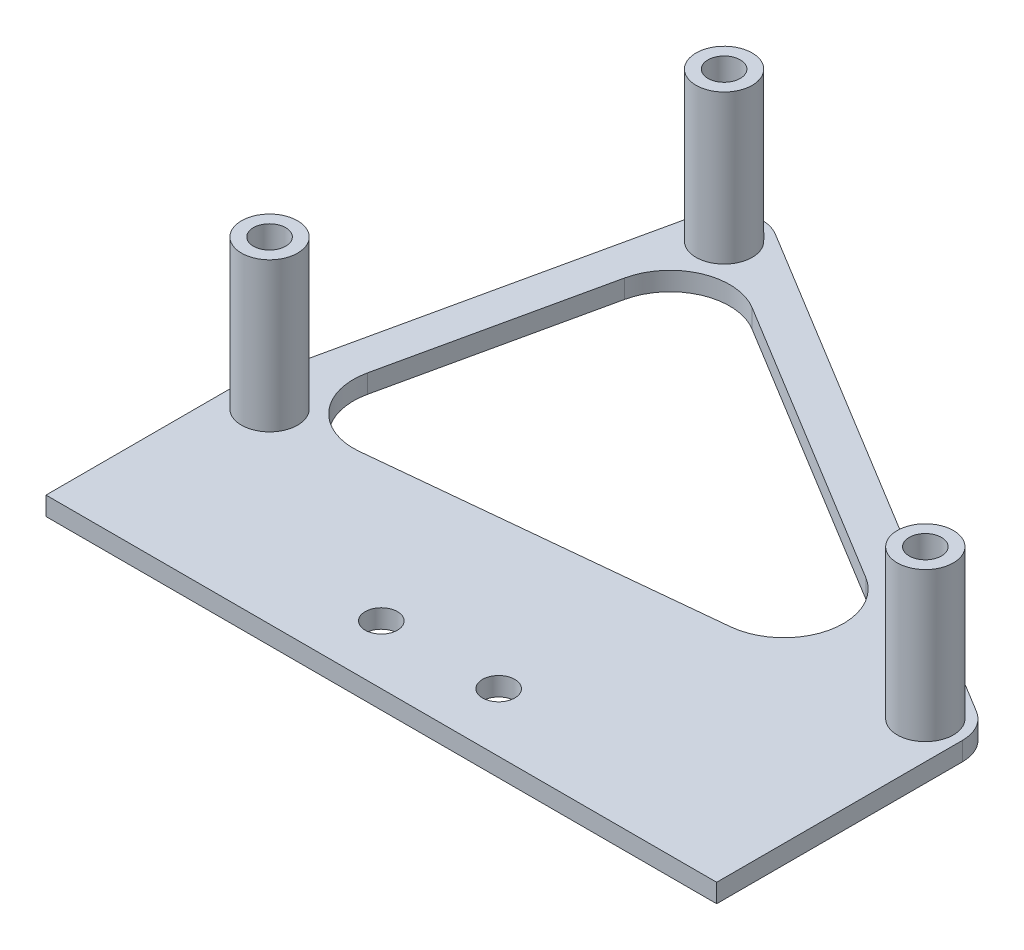
SolidWorks part; units mm, degrees
ref_plane "Front Plane" through (0, 0, 0) normal (0, 0, 1) x (1, 0, 0)
ref_plane "Top Plane" through (0, 0, 0) normal (0, 1, 0) x (1, 0, 0)
ref_plane "Right Plane" through (0, 0, 0) normal (1, 0, 0) x (0, 0, -1)
sketch "Sketch1" plane through (0, 0, 0) normal (0, 1, 0) x (1, 0, 0)
  line L0 (-54.2925, -20.955) -> (-40.3225, 42.545) construction
  line L5 (-40.3225, 42.545) -> (47.3075, -10.795) construction
  line L6 (47.3075, -10.795) -> (-54.2925, -20.955) construction
  line L7 (-47.3075, 10.795) -> (47.3075, -10.795) construction
  circle A0 centre (-40.3225, 42.545) radius 2.75
  circle A1 centre (-54.2925, -20.955) radius 2.75
  circle A2 centre (47.3075, -10.795) radius 2.75
  point P8 (0, 0)
  dimension "D5" = 5.5
  dimension "D1" = 10.16
  dimension "D2" = 101.6
  dimension "D3" = 13.97
  dimension "D4" = 63.5
sketch "Sketch2" plane through (0, 0, 0) normal (0, 1, 0) x (1, 0, 0)
  line L6 (-60.4942, -19.5906) -> (-46.5242, 43.9094)
  line L7 (-37.0208, 47.9692) -> (50.6092, -5.3708)
  line L9 (47.9393, -17.1135) -> (-53.6607, -27.2735)
  arc A0 (-46.5242, 43.9094) -> (-37.0208, 47.9692) centre (-40.3225, 42.545) cw
  arc A1 (50.6092, -5.3708) -> (47.9393, -17.1135) centre (47.3075, -10.795) cw
  arc A2 (-53.6607, -27.2735) -> (-60.4942, -19.5906) centre (-54.2925, -20.955) cw
  dimension "D1" = 6.35
extrude "Boss-Extrude1" add sketch "Sketch2" against normal blind 3.175
shell "Shell1" thickness 6.35 removed face at (-16.3218, -3.175, -3.7119) removed face at (-16.3218, 0, -3.7119)
fillet "Fillet1" radius 10.16 3 edges at (47.3075, -1.5875, 10.795) (-54.2925, -1.5875, 20.955) (-40.3225, -1.5875, -42.545)
sketch "Sketch3" plane through (0, 0, 0) normal (0, 1, 0) x (1, 0, 0)
  line L0 (-60.6425, -20.955) -> (-60.6425, -52.705)
  line L5 (-60.6425, -52.705) -> (53.6575, -52.705)
  line L6 (53.6575, -52.705) -> (53.6575, -10.795)
  line L7 (-60.6425, -33.655) -> (53.6575, -33.655) construction
  line L8 (-53.6607, -27.2735) -> (47.9393, -17.1135) construction
  line L9 (-53.6607, -27.2735) -> (47.9393, -17.1135)
  arc A1 (-60.4942, -19.5906) -> (-53.6607, -27.2735) centre (-54.2925, -20.955) ccw construction
  arc A2 (47.9393, -17.1135) -> (50.6092, -5.3708) centre (47.3075, -10.795) ccw construction
  arc A3 (47.9393, -17.1135) -> (53.6575, -10.795) centre (47.3075, -10.795) ccw
  arc A4 (-60.6425, -20.955) -> (-53.6607, -27.2735) centre (-54.2925, -20.955) ccw
  dimension "D1" = 12.7
  dimension "D2" = 19.05
extrude "Boss-Extrude2" add sketch "Sketch3" against normal up to surface (3.175 mm away) up to face at (-16.3218, -3.175, -3.7119)
extrude "Cut-Extrude1" cut sketch "Sketch1" against normal through all contours A1 | A2 | A0 region at (-54.2925, 0, 20.955) region at (47.3075, 0, 10.795)
sketch "Sketch5" plane through (0, 0, 0) normal (0, 1, 0) x (1, 0, 0)
  circle A0 centre (47.3075, -10.795) radius 2.75 construction
  circle A1 centre (-54.2925, -20.955) radius 2.75 construction
  circle A2 centre (-40.3225, 42.545) radius 2.75 construction
  circle A3 centre (47.3075, -10.795) radius 2.75
  circle A4 centre (-54.2925, -20.955) radius 2.75
  circle A5 centre (-40.3225, 42.545) radius 2.75
extrude "Extrude-Thin1" add sketch "Sketch5" along normal blind 25.4 thin thin type one direction wall 2.032
sketch "Sketch6" plane through (0, 0, 0) normal (0, 1, 0) x (1, 0, 0)
  line L0 (6.5075, -42.705) -> (-13.4925, -42.705) construction
  line L1 (-13.4925, -42.705) -> (53.6575, -42.705) construction
  line L2 (53.6575, -52.705) -> (53.6575, -10.795) construction
  line L3 (6.5075, -42.705) -> (-60.6425, -42.705) construction
  line L4 (-60.6425, -20.955) -> (-60.6425, -52.705) construction
  line L5 (-60.6425, -52.705) -> (53.6575, -52.705) construction
  circle A0 centre (-13.4925, -42.705) radius 2.75
  circle A1 centre (6.5075, -42.705) radius 2.75
  dimension "D3" = 5.5
  dimension "D1" = 20
  dimension "D2" = 10
extrude "Cut-Extrude2" cut sketch "Sketch6" against normal through all
